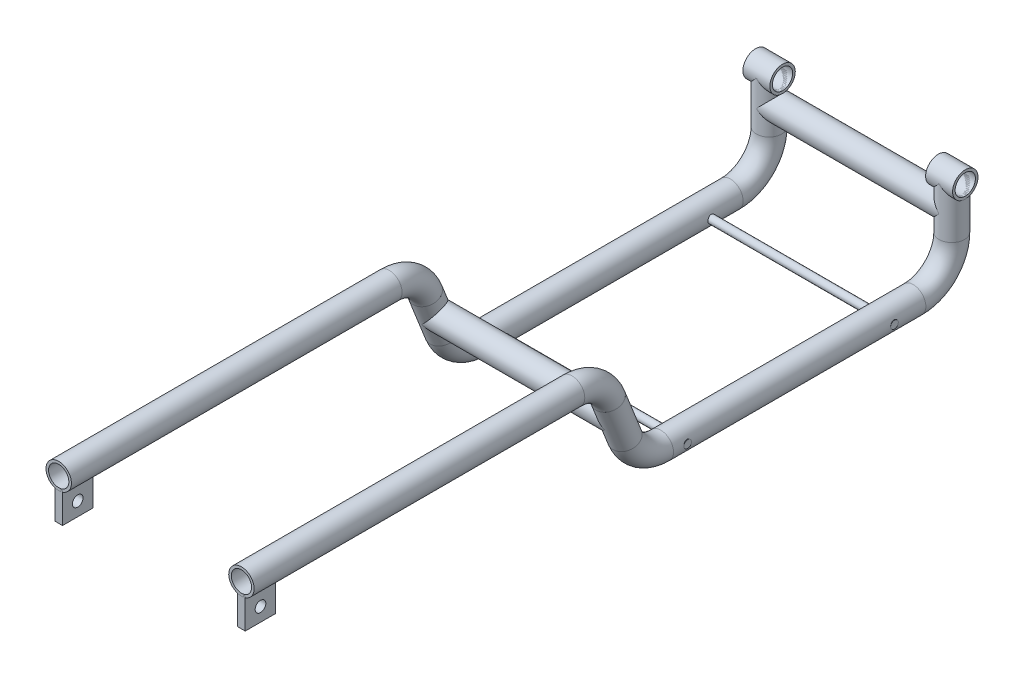
SolidWorks part; units mm, degrees
note: The reader was unsure of these and kept them because the rebuilt part matched: shared geometry of "Croquis8<2>".
ref_plane "Alzado" through (0, 0, 0) normal (0, 0, 1) x (1, 0, 0)
ref_plane "Planta" through (0, 0, 0) normal (0, 1, 0) x (1, 0, 0)
ref_plane "Vista lateral" through (0, 0, 0) normal (1, 0, 0) x (0, 0, -1)
sketch "Croquis1" plane through (0, 0, 0) normal (1, 0, 0) x (0, 0, -1)
  line L0 (-500, 120) -> (0, 120) construction
  line L1 (0, 120) -> (0, 0) construction
  line L2 (0, 0) -> (433, 0) construction
  line L3 (433, 0) -> (433, 114) construction
  dimension "D1" = 500
  dimension "D2" = 120
  dimension "D3" = 433
  dimension "D4" = 114
ref_plane "Plano1" through (120, 0, 0) normal (1, 0, 0) x (0, 0, -1)
sketch "Croquis2" plane through (120, 0, 0) normal (1, 0, 0) x (0, 0, -1)
  line L0 (-500, 120) -> (0, 120) construction
  line L1 (3.565, 32.1053) -> (-18.5154, 87.8947)
  line L2 (0, 120) -> (0, 0) construction
  line L4 (0, 0) -> (433, 0) construction
  line L5 (433, 0) -> (433, 114) construction
  line L6 (-500, 120) -> (-65.7504, 120)
  line L8 (50.8, 0) -> (382.2, 0)
  line L9 (433, 50.8) -> (433, 114)
  arc A0 (-18.5154, 87.8947) -> (-65.7504, 120) centre (-65.7504, 69.2) ccw
  arc A1 (382.2, 0) -> (433, 50.8) centre (382.2, 50.8) ccw
  arc A2 (3.565, 32.1053) -> (50.8, 0) centre (50.8, 50.8) ccw
  point P0 (-500, 120)
  point P2 (433, 114)
  dimension "D1" = 50.8
  dimension "D2" = 50.8
  dimension "D3" = 50.8
  dimension "D4" = 60
  dimension "D5" = 63.2
  dimension "D6" = 90
  dimension "D7" = 331.4
  dimension "D8" = 111.593
  dimension "D9" = 111.593
  dimension "D10" = 434.2496
ref_plane "Plano3" through (0, 114, -433) normal (0, 1, 0) x (1, 0, 0)
sketch "Croquis4" plane through (0, 114, -433) normal (0, 1, 0) x (1, 0, 0)
  line L0 (-137.7, 0) -> (137.7, 0) construction
  line L1 (-137.7, 0) -> (-102.3, 0)
  line L2 (137.7, 0) -> (102.3, 0)
  point P2 (-120, -3.0919)
  point P3 (87.8441, 0)
  dimension "D1" = 17.7
  dimension "D2" = 17.7
other "Miembro estructural5" corner treatment miter
ref_plane "Plano13" through (120, 120, 500) normal (0, 0, -1) x (0, 1, 0)
sketch "Sketch1" plane through (120, 120, 500) normal (0, 0, -1) x (0, 1, 0)
  circle A0 centre (0, 0) radius 13.3223
  circle A1 centre (0, 0) radius 16.7005
  circle A2 centre (0, 0) radius 12.7 construction
  point P5 (0, 0)
  dimension "In_dia" = 26.6446
  dimension "Out_dia" = 33.401
  dimension "D1" = 25.4
ref_plane "Plano14" through (0, 82.3269, 32.5834) normal (0, 0.9298, 0.368) x (1, 0, 0)
ref_plane "Plano15" through (0, 54.4322, 21.5432) normal (0, 0.9298, 0.368) x (1, 0, 0)
other "Miembro estructural2" corner treatment miter
ref_plane "Plano5" through (-137.7, 114, -433) normal (1, 0, 0) x (0, 0, -1)
sketch "Sketch12" plane through (-137.7, 114, -433) normal (1, 0, 0) x (0, 0, -1)
  circle A0 centre (0, 0) radius 13.3223
  circle A1 centre (0, 0) radius 16.7005
  circle A2 centre (0, 0) radius 12.7 construction
  point P5 (0, 0)
  dimension "In_dia" = 26.6446
  dimension "Out_dia" = 33.401
  dimension "D1" = 25.4
sketch "Croquis8" plane through (137.7, 0, 0) normal (1, 0, 0) x (0, 0, -1)
  circle A1 centre (433, 114) radius 13.3223 construction
  circle A2 centre (433, 114) radius 13.3223
sketch "Croquis9" plane through (0, 57.2491, 14.4258) normal (0, -0.9298, -0.368) x (1, 0, 0)
  line L2 (120, -7.4752) -> (-120, -7.4752)
other "Miembro estructural3" corner treatment miter
ref_plane "Plano7" through (120, 60, 7.4752) normal (-1, 0, 0) x (0, -0.368, 0.9298)
sketch "Sketch13" plane through (120, 60, 7.4752) normal (-1, 0, 0) x (0, -0.368, 0.9298)
  circle A0 centre (0, 0) radius 13.3223
  circle A1 centre (0, 0) radius 16.7005
  circle A2 centre (0, 0) radius 12.7 construction
  point P5 (0, 0)
  dimension "In_dia" = 26.6446
  dimension "Out_dia" = 33.401
  dimension "D1" = 25.4
ref_plane "Plano8" through (0, 80, 0) normal (0, 1, 0) x (1, 0, 0)
sketch "Croquis11" plane through (0, 80, 0) normal (0, 1, 0) x (1, 0, 0)
  line L0 (-120, 433) -> (120, 433)
  line L1 (-137.7, 433) -> (-102.3, 433) construction
other "Miembro estructural4" corner treatment miter
ref_plane "Plano9" through (-120, 80, -433) normal (1, 0, 0) x (0, 0, -1)
sketch "Sketch14" plane through (-120, 80, -433) normal (1, 0, 0) x (0, 0, -1)
  circle A0 centre (0, 0) radius 13.3223
  circle A1 centre (0, 0) radius 16.7005
  circle A2 centre (0, 0) radius 12.7 construction
  point P5 (0, 0)
  dimension "In_dia" = 26.6446
  dimension "Out_dia" = 33.401
  dimension "D1" = 25.4
ref_plane "Plano10" through (98.26, 0, 0) normal (1, 0, 0) x (0, 0, -1)
ref_plane "Plano11" through (-1.74, 0, 0) normal (1, 0, 0) x (0, 0, -1)
ref_plane "Plano12" through (68.26, 0, 0) normal (1, 0, 0) x (0, 0, -1)
mirror "Simetría3" about plane through (0, 0, 0) normal (1, 0, 0) of bodies 132 133 134 135 136 137 138
extrude "Cortar-Extruir1" cut sketch "Croquis8" against normal blind 50
sketch "Croquis12" plane through (120, 0, 0) normal (1, 0, 0) x (0, 0, -1)
  line L0 (-500, 106.0864) -> (-460, 106.0864)
  line L1 (-500, 136.7005) -> (-500, 103.2995) construction
  line L2 (-460, 106.0864) -> (-460, 66.0864)
  line L3 (-460, 66.0864) -> (-500, 66.0864)
  line L4 (-500, 66.0864) -> (-500, 106.0864)
  circle A0 centre (-480, 84.0864) radius 7
  dimension "D1" = 20
  dimension "D2" = 18
extrude "Saliente-Extruir1" add sketch "Croquis12" along normal mid plane 10 separate body
mirror "Simetría5" about plane through (0, 0, 0) normal (1, 0, 0) of bodies 148
extrude "Cortar-Extruir2" cut sketch "Croquis8<2>" against normal blind 320
sketch "Croquis8<2>" plane through (137.7, 0, 0) normal (1, 0, 0) x (0, 0, -1) same geometry as "Croquis8"
sketch "Croquis13" plane through (0, 0, 0) normal (1, 0, 0) x (0, 0, -1)
  circle A0 centre (341.03, 0) radius 5
  circle A1 centre (69.42, 0) radius 5
  dimension "D1" = 41.17
  dimension "D2" = 18.62
extrude "Saliente-Extruir2" add sketch "Croquis13" along normal mid plane 273.4 separate body
sketch "Croquis14" plane through (0, 0, 0) normal (1, 0, 0) x (0, 0, -1)
  circle A1 centre (433, 80) radius 16.7005
  circle A2 centre (433, 80) radius 16.7005
  circle A3 centre (433, 80) radius 13.3223
  circle A4 centre (433, 80) radius 13.3223
  circle A5 centre (-7.4752, 60) radius 16.7005
  circle A6 centre (-7.4752, 60) radius 16.7005
  circle A7 centre (-7.4752, 60) radius 13.3223
  circle A8 centre (-7.4752, 60) radius 13.3223
  dimension "D1" = 0
  dimension "D2" = 0
  dimension "D3" = 0
  dimension "D4" = 0
